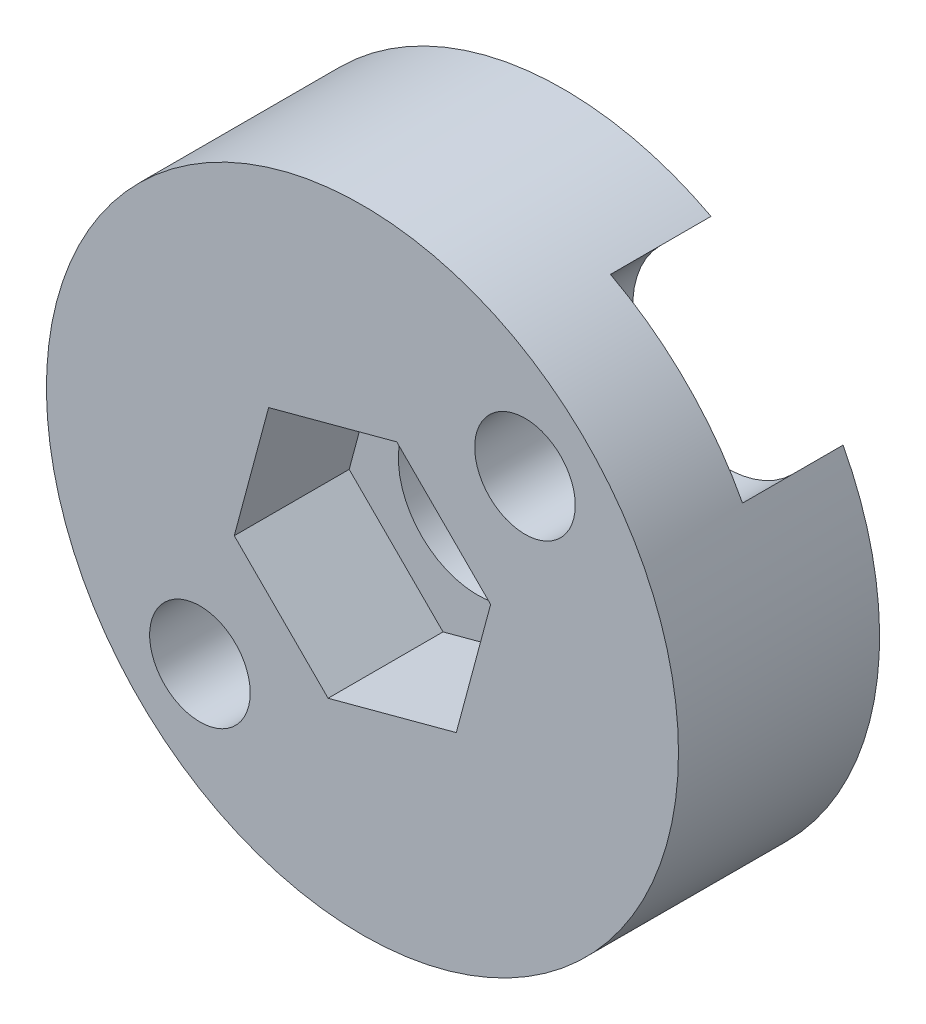
SolidWorks part; units mm, degrees
ref_plane "Plano frontal" through (0, 0, 0) normal (0, 0, 1) x (1, 0, 0)
ref_plane "Plano superior" through (0, 0, 0) normal (0, 1, 0) x (1, 0, 0)
ref_plane "Plano direito" through (0, 0, 0) normal (1, 0, 0) x (0, 0, -1)
sketch "Esboço1" plane through (0, 0, 0) normal (0, 0, 1) x (1, 0, 0)
  line L1 (5.6569, 5.6569) -> (-5.6569, 5.6569) construction
  line L2 (5.6569, 5.6569) -> (5.6569, -5.6569) construction
  line L3 (5.6569, -5.6569) -> (-5.6569, -5.6569) construction
  line L4 (-5.6569, 5.6569) -> (-5.6569, -5.6569) construction
  line L5 (5.6569, 5.6569) -> (-5.6569, -5.6569) construction
  line L6 (5.6569, -5.6569) -> (-5.6569, 5.6569) construction
  circle A0 centre (0, 0) radius 11
  circle A1 centre (5.6569, 5.6569) radius 1.75
  circle A2 centre (-5.6569, 5.6569) radius 1.75 construction
  circle A3 centre (-5.6569, -5.6569) radius 1.75
  circle A4 centre (5.6569, -5.6569) radius 1.75 construction
  circle A5 centre (0, 0) radius 2.75
  dimension "D1" = 22
  dimension "D3" = 3.5
  dimension "D4" = 5.5
  dimension "D2" = 16
extrude "Ressalto-extrusão1" add sketch "Esboço1" along normal blind 7
sketch "Esboço10" plane through (0, 0, 7) normal (0, 0, 1) x (1, 0, 0)
  line L0 (-5.6569, -5.6569) -> (5.6569, 5.6569) construction
  line L1 (-1.1954, -4.4614) -> (3.266, -3.266)
  line L2 (3.266, -3.266) -> (4.4614, 1.1954)
  line L3 (4.4614, 1.1954) -> (1.1954, 4.4614)
  line L4 (1.1954, 4.4614) -> (-3.266, 3.266)
  line L5 (-3.266, 3.266) -> (-4.4614, -1.1954)
  line L6 (-4.4614, -1.1954) -> (-1.1954, -4.4614)
  line L7 (0, 0) -> (-5.369, 5.369) construction
  circle A0 centre (0, 0) radius 4 construction
  point P1 (0, 0)
  point P14 (-3.266, 3.266)
  dimension "D1" = 8
extrude "Corte-extrusão5" cut sketch "Esboço10" against normal blind 4
sketch "Esboço12" plane through (0, 0, 0) normal (0, 0, -1) x (-1, 0, 0)
  line L1 (-3.3588, 7.955) -> (-5.1328, 9.729)
  line L4 (-7.955, 3.3588) -> (-9.729, 5.1328)
  circle A12 centre (0, 0) radius 11 construction
  arc A13 (-7.955, 3.3588) -> (-3.3588, 7.955) centre (-5.6569, 5.6569) ccw
  circle A14 centre (0, 0) radius 11
  arc A15 (-5.1328, 9.729) -> (6.675, 8.7433) centre (0, 0) ccw
  point P21 (-2.4069, 5.6569)
  circle M11 centre (0, 0) radius 11
  circle M12 centre (-5.6569, 5.6569) radius 1.75
  dimension "D2" = 0
extrude "Corte-extrusão6" cut sketch "Esboço12" against normal offset from surface (3.5 mm away) 3.5 contours L4 A13 L1 M11 M12 region at (3.432, 3.432, 0) up to face at (0, 0, 7)
ref_axis "Eixo1" through (0, 0, 3) along (0, 0, -1)
pattern_circular "PadrãoCircular1" count 2 over 360 about axis through (0, 0, 3) along (0, 0, -1) of "Corte-extrusão6"
